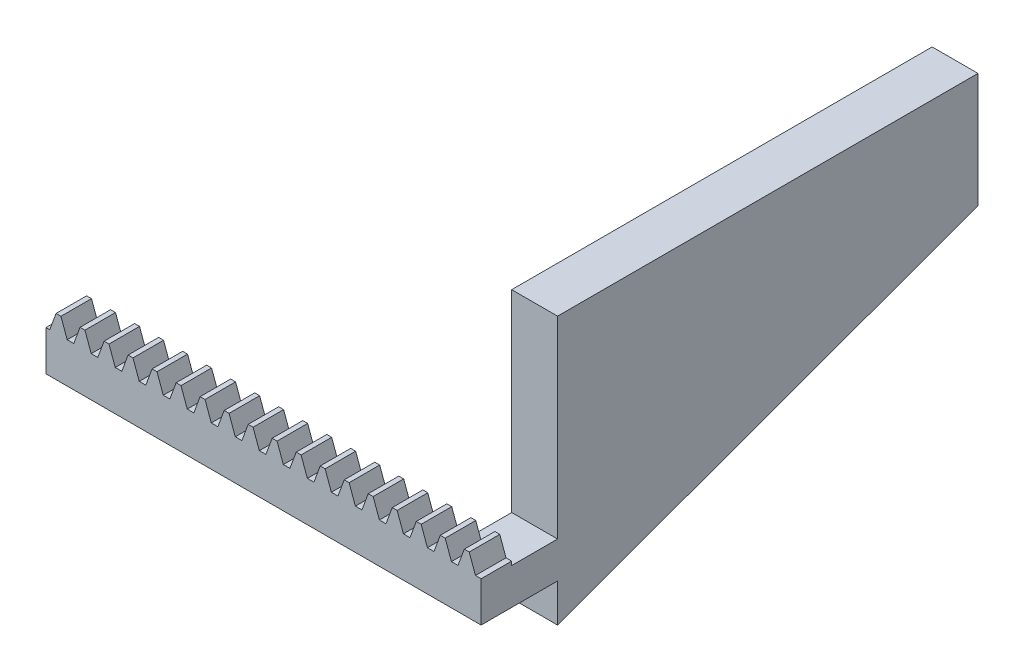
SolidWorks part; units mm, degrees
extrude "Blank" add sketch "BlankSke" against normal blind 8
sketch "BlankSke" plane through (0, 0, 0) normal (0, 0, 1) x (1, 0, 0)
  line L1 (0, 0) -> (120, 0)
  line L2 (0, 0) -> (0, 16)
  line L3 (0, 16) -> (120, 16)
  line L4 (120, 0) -> (120, 16)
  dimension "Length" = 120
ref_plane "Plane1" through (0, 0, 0) normal (0, 0, 1) x (1, 0, 0)
ref_plane "Plane2" through (0, 0, 0) normal (0, 1, 0) x (1, 0, 0)
ref_plane "Plane3" through (0, 0, 0) normal (1, 0, 0) x (0, 0, -1)
sketch "HoldingSke" plane through (0, 0, 0) normal (0, 1, 0) x (1, 0, 0)
  line L0 (0, 0) -> (0.0696, 0.4951)
  line L1 (-15, 0) -> (100, 0) construction
  line L2 (0, 0) -> (-2.1039, 2.3779)
  line L3 (0, 0) -> (-11.863, 4.5341)
  line L4 (0, 0) -> (8.0624, 3.0949)
  line L5 (0, 0) -> (-23.7986, -8.8762)
  line L6 (0, 0) -> (-10.5278, -7.1032)
  line L9 (-71.009, 38.7566) -> (41.7541, 79.799)
  line L10 (-76.2, 4.3779) -> (-62.2, 4.3779)
  line L11 (0, 0) -> (-8, 0)
  line L12 (-76.2, 101.6) -> (-76.133, 101.6)
  line L13 (24.9733, 27.94) -> (52.9518, 28.4284)
  line L14 (24.9733, 27.94) -> (24.9743, 27.94)
  line L15 (24.9733, 27.94) -> (100.4006, 29.5858)
  circle A0 centre (0, 0) radius 19.05
  circle A1 centre (0, 0) radius 7
  circle A2 centre (0, 0) radius 12.7
  dimension "Num_teeth" = 21
  dimension "Width" = 8
  dimension "Length" = 120
  dimension "Pitch_height" = 14
sketch "TooCutSkeIll" plane through (0, 0, 0) normal (0, 0, 1) x (1, 0, 0)
  line L0 (-2.4806, 15.9474) -> (-0.9819, 11.8296)
  line L1 (-0.5111, 11.5) -> (0.5111, 11.5)
  line L2 (0.9819, 11.8296) -> (2.4806, 15.9474)
  line L3 (120, 16) -> (0, 16) construction
  line L4 (0, 0) -> (0, 64.897) construction
  line L5 (-13.208, 14) -> (12.954, 14) construction
  line L6 (0, 0) -> (120, 0) construction
  line L7 (1.7718, 14) -> (1.7718, 48.7463) construction
  line L8 (-1.7718, 14) -> (-1.7718, 48.7463) construction
  line L9 (2.5558, 16) -> (2.5558, 16.0254)
  line L10 (-2.5558, 16) -> (-2.5558, 16.0254)
  line L11 (-2.5558, 16.0254) -> (2.5558, 16.0254)
  arc A0 (0.5111, 11.5) -> (0.9819, 11.8296) centre (0.5111, 12.001) ccw
  arc A1 (-0.9819, 11.8296) -> (-0.5111, 11.5) centre (-0.5111, 12.001) ccw
  arc A2 (2.5558, 16) -> (2.4806, 15.9474) centre (2.5558, 15.92) ccw
  arc A3 (-2.4806, 15.9474) -> (-2.5558, 16) centre (-2.5558, 15.92) ccw
  dimension "Addendum_plus" = 2.0254
  dimension "Pitch_height" = 14
  dimension "Pressure_angle" = 20
  dimension "Gap_width" = 3.5436
  dimension "Dedendum" = 2.5
extrude "ToothCutIll" [suppressed] cut sketch "TooCutSkeIll" against normal through all
sketch "TooCutSkeSim" plane through (0, 0, 0) normal (0, 0, 1) x (1, 0, 0)
  line L0 (0.8619, 11.5) -> (-0.8619, 11.5)
  line L1 (2.509, 16.0254) -> (0.8619, 11.5)
  line L2 (0, 17.4625) -> (0, 53.467) construction
  line L3 (2.509, 16.0254) -> (-2.509, 16.0254)
  line L6 (-2.509, 16.0254) -> (-0.8619, 11.5)
  line L9 (-1.7718, 14) -> (1.7718, 14) construction
  line L10 (0, 0) -> (120, 0) construction
  line L11 (1.7718, 14) -> (1.7718, 53.467) construction
  line L12 (-1.7718, 14) -> (-1.7718, 53.467) construction
  dimension "Addendum_plus" = 2.0254
  dimension "Pitch_height" = 14
  dimension "Pressure_angle" = 20
  dimension "Gap_width" = 3.5436
  dimension "Dedendum" = 2.5
extrude "ToothCutSim" cut sketch "TooCutSkeSim" against normal through all
pattern_linear "TeethCuts" count 21 spacing 6.2832 along (1, 0, 0) of "ToothCutIll", "ToothCutSim"
sketch "Sketch1" plane through (120, 0, 0) normal (1, 0, 0) x (0, 0, -1)
  line L0 (0, 1) -> (8, 1)
  line L1 (0, 0) -> (0, 11.5) construction
  line L2 (8, 0) -> (8, 11.5) construction
  line L3 (8, 1) -> (8, 0)
  line L4 (8, 0) -> (0, 0)
  line L5 (0, 0) -> (0, 1)
  dimension "D1" = 1
extrude "Cut-Extrude1" cut sketch "Sketch1" against normal through all
sketch "Sketch2" plane through (120, 0, 0) normal (1, 0, 0) x (0, 0, -1)
  line L0 (8, 1) -> (20, 1)
  line L1 (20, 1) -> (20, -9)
  line L2 (20, -9) -> (130, 31)
  line L3 (130, 31) -> (130, 61)
  line L4 (130, 61) -> (20, 61)
  line L5 (20, 61) -> (20, 10.5)
  line L6 (20, 10.5) -> (8, 10.5)
  line L7 (8, 1) -> (8, 11.5) construction
  line L8 (8, 10.5) -> (8, 1)
  dimension "D1" = 9.5
  dimension "D2" = 110
  dimension "D3" = 70
  dimension "D4" = 30
  dimension "D5" = 10
  dimension "D6" = 12
extrude "Boss-Extrude2" add sketch "Sketch2" against normal blind 12
sketch "Sketch3" plane through (0, 0, 0) normal (0, 0, 1) x (1, 0, 0)
  line L0 (0, 1) -> (0, 11.5)
  line L1 (0, 11.5) -> (0, 1) construction
  line L2 (0.8619, 11.5) -> (2.4997, 16)
  line L3 (2.4997, 16) -> (3.7834, 16)
  line L4 (3.7834, 16) -> (5.4213, 11.5)
  line L5 (5.4213, 11.5) -> (6.1613, 11.5)
  line L6 (5.4213, 11.5) -> (7.1451, 11.5) construction
  line L7 (6.1613, 11.5) -> (6.1613, 1)
  line L8 (0, 1) -> (120, 1) construction
  line L9 (6.1613, 1) -> (0, 1)
  arc A0 (0, 11.5) -> (0.8619, 11.5) centre (0.4309, 11.5) cw
  dimension "D1" = 0.74
extrude "Cut-Extrude2" cut sketch "Sketch3" against normal through all
equation "' \"Module@HoldingSke\" = 6.35"
equation "' \"Num_teeth@HoldingSke\" = 12"
equation "' \"Ap@HoldingSke\" =  20"
equation "' \"Ap@HoldingSke\" = 20"
equation "' \"Width@HoldingSke\" = 0.25 * 25.4"
equation "' \"Show_teeth@HoldingSke\" = 500"
equation "' \"Backlash@HoldingSke\" = 0.009 * 25.4"
equation "' \"Addendum_fac@HoldingSke\" = 1.0"
equation "' \"Dedendum_fac@HoldingSke\" = 1.25"
equation "' \"Dedendum_add@HoldingSke\" = 0.00005 * 25.4"
equation "' \"Clearance_fac@HoldingSke\" = 0.25"
equation "' \"Pitch_height@HoldingSke\" = 1 * 25.4"
equation "' \"Length@HoldingSke\" = 4.71 * 25.4"
equation "\"Pitch@HoldingSke\" = 1 / \"Module@HoldingSke\""
equation "\"MPH@HoldingSke\" = \"Dedendum_fac@HoldingSke\" / \"Pitch@HoldingSke\" + 2 * \"Dedendum_add@HoldingSke\" + 0.002 * 25.4"
equation "\"MPH@HoldingSke\" = ((sgn( \"MPH@HoldingSke\" - \"Pitch_height@HoldingSke\")+1)*( \"MPH@HoldingSke\" - \"Pitch_height@HoldingSke\"))/2 + \"Pitch_height@HoldingSke\""
equation "\"Blank_height@BlankSke\" = \"Pitch_height@HoldingSke\" + \"Addendum_fac@HoldingSke\"  / \"Pitch@HoldingSke\" "
equation "\"Length@BlankSke\" =  \"Length@HoldingSke\""
equation "\"Face_width@Blank\" = \"Width@HoldingSke\""
equation "\"Pressure_angle@TooCutSkeIll\" = \"Ap@HoldingSke\""
equation "\"Addendum_plus@TooCutSkeIll\" =  \"Addendum_fac@HoldingSke\"  / \"Pitch@HoldingSke\" + 0.001 *25.4"
equation "\"Dedendum@TooCutSkeIll\" = \"Dedendum_fac@HoldingSke\"  / \"Pitch@HoldingSke\""
equation "\"Pitch_height@TooCutSkeIll\" =  \"MPH@HoldingSke\""
equation "\"Gap_width@TooCutSkeIll\" = 3.14159265 / 2 / \"Pitch@HoldingSke\" + 6 * \"Backlash@HoldingSke\""
equation "\"Pressure_angle@TooCutSkeSim\" = \"Ap@HoldingSke\""
equation "\"Addendum_plus@TooCutSkeSim\" =  \"Addendum_fac@HoldingSke\"  / \"Pitch@HoldingSke\" + 0.001 * 25.4"
equation "\"Dedendum@TooCutSkeSim\" = \"Dedendum_fac@HoldingSke\"  / \"Pitch@HoldingSke\""
equation "\"Pitch_height@TooCutSkeSim\" =  \"MPH@HoldingSke\""
equation "\"Gap_width@TooCutSkeSim\" = 3.14159265 / 2 / \"Pitch@HoldingSke\" + 6 * \"Backlash@HoldingSke\""
equation "\"Root_fillet@TooCutSkeIll\" = \"Clearance_fac@HoldingSke\" / \"Pitch@HoldingSke\" + \"Dedendum_add@HoldingSke\""
equation "\"Break_rad@TooCutSkeIll\" = 0.02 / \"Pitch@HoldingSke\" * 2"
equation "\"Linear_pitch@TeethCuts\" = 3.14159265 / \"Pitch@HoldingSke\""
equation "\"Num_teeth@HoldingSke\" = int( ( \"Length@HoldingSke\" + 0 ) / (3.14159265 / \"Pitch@HoldingSke\")) + 0.9999  + 1"
equation " \"Num_teeth@TeethCuts\" = int( \"Show_teeth@HoldingSke\" ) + 1"
equation " \"Num_teeth@TeethCuts\" = ((sgn( \"Num_teeth@TeethCuts\" - \"Num_teeth@HoldingSke\" )-1)*( \"Num_teeth@TeethCuts\" - \"Num_teeth@HoldingSke\" ))/-2+ \"Num_teeth@HoldingSke\""
equation " \"Num_teeth@TeethCuts\" = ((sgn( \"Num_teeth@TeethCuts\" - 2.0)+1)*( \"Num_teeth@TeethCuts\" - 2.0))/2 +2.0"
